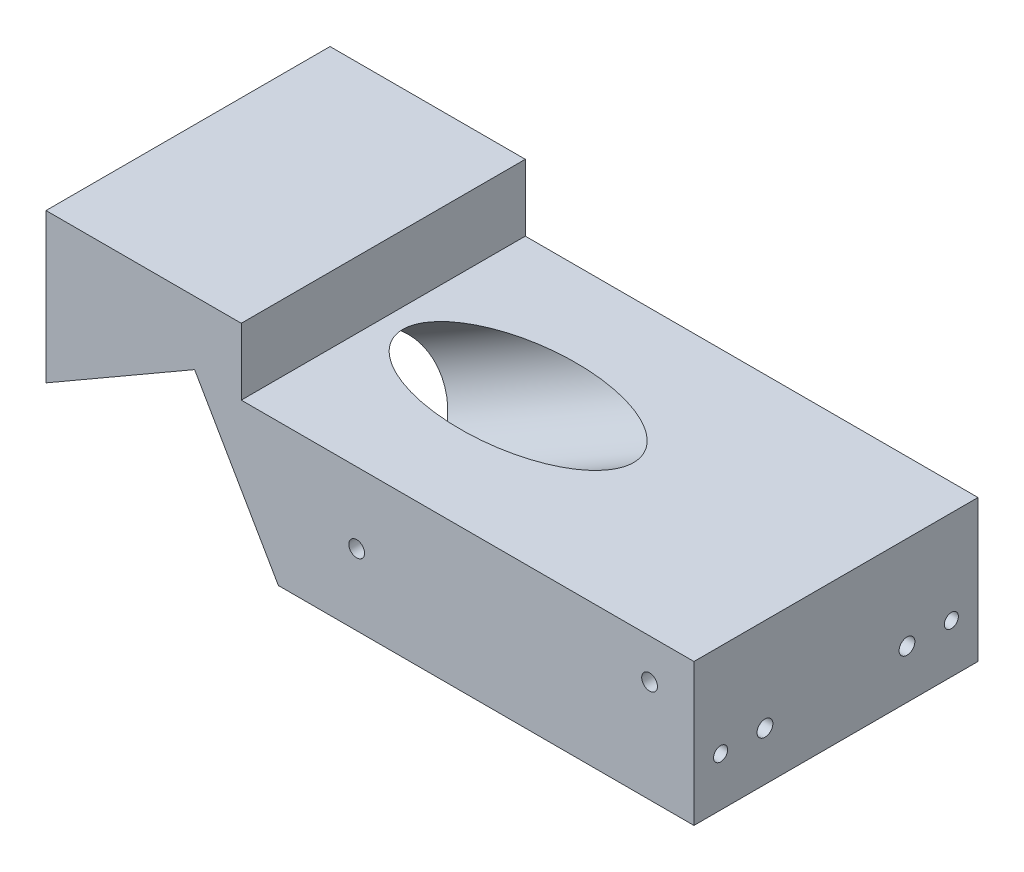
SolidWorks part; units mm, degrees
material "6061-T4 (SS)"
ref_plane "Front Plane" through (0, 0, 0) normal (0, 0, 1) x (1, 0, 0)
ref_plane "Top Plane" through (0, 0, 0) normal (0, 1, 0) x (1, 0, 0)
ref_plane "Right Plane" through (0, 0, 0) normal (1, 0, 0) x (0, 0, -1)
sketch "Sketch1" plane through (0, 0, 0) normal (0, 1, 0) x (1, 0, 0)
  line L1 (-36.5, 16) -> (36.5, 16)
  line L2 (-36.5, 16) -> (-36.5, -16)
  line L3 (-36.5, -16) -> (36.5, -16)
  line L4 (36.5, 16) -> (36.5, -16)
  line L5 (-36.5, 16) -> (36.5, -16) construction
  line L6 (-36.5, -16) -> (36.5, 16) construction
  point P0 (0, 0)
  dimension "D1" = 73
  dimension "D2" = 32
extrude "Boss-Extrude1" add sketch "Sketch1" along normal blind 16
sketch "Sketch78" plane through (0, 0, 16) normal (0, 0, 1) x (1, 0, 0)
  line L1 (-36.5, 16) -> (-14.5, 16)
  line L2 (-36.5, 16) -> (-36.5, 23.5)
  line L3 (-36.5, 23.5) -> (-14.5, 23.5)
  line L4 (-14.5, 16) -> (-14.5, 23.5)
  dimension "D1" = 7.5
  dimension "D2" = 22
extrude "Boss-Extrude4" add sketch "Sketch78" against normal up to surface (32 mm away) up to face at (0, 8, -16)
sketch "Sketch79" plane through (0, 0, -16) normal (0, 0, -1) x (-1, 0, 0)
  line L0 (-32.5, 1.97) -> (23.61, 1.97) construction
  line L1 (-32.5, 1.97) -> (-32.5, 29.2) construction
  line L2 (23.61, 1.97) -> (-20.8992, 27.6674) construction
  line L3 (33.135, 1.97) -> (34.135, 1.97) construction
  line L4 (14.4951, 7.2325) -> (19.7576, 16.3474)
  line L5 (19.7576, 16.3474) -> (36.5, 6.6812)
  line L6 (36.5, 23.5) -> (36.5, 0) construction
  line L7 (14.4951, 7.2325) -> (10.3194, 0)
  line L8 (-36.5, 0) -> (36.5, 0) construction
  line L9 (10.3194, 0) -> (36.5, 0)
  line L10 (36.5, 0) -> (36.5, 6.6812)
  circle A0 centre (23.61, 1.97) radius 9.525 construction
  circle A1 centre (23.61, 1.97) radius 10.525 construction
  dimension "D4" = 19.05
  dimension "D1" = 27.23
  dimension "D2" = 56.11
  dimension "D3" = 30
  dimension "D5" = 1
extrude "Cut-Extrude23" cut sketch "Sketch79" against normal blind 41
sketch "Sketch26" plane through (0, 0, 0) normal (0, -1, 0) x (1, 0, 0)
  line L0 (-10.3194, 16) -> (36.5, 16) construction
  line L1 (36.5, -16) -> (42.85, -16)
  line L2 (36.5, -16) -> (36.5, 16)
  line L3 (36.5, 16) -> (42.85, 16)
  line L4 (42.85, -16) -> (42.85, 16)
  dimension "D1" = 6.35
sketch "Sketch15" plane through (-36.5, 0, 0) normal (-1, 0, 0) x (0, 0, 1)
  line L0 (-10, 14.6812) -> (10, 14.6812) construction
  line L1 (-10, 14.6812) -> (-16, 14.6812) construction
  line L3 (10, 14.6812) -> (16, 14.6812) construction
  line L6 (16, 23.5) -> (16, 6.6812) construction
  line L7 (-16, 23.5) -> (-16, 6.6812) construction
  line L9 (16, 6.6812) -> (-16, 6.6812) construction
  dimension "D3" = 20
  dimension "D4" = 8
sketch "Sketch14" plane through (-13.4261, 5.3809, -20) normal (-0.866, -0.5, 0) x (0, 0, 1)
  line L0 (4, 2.138) -> (20, 2.138) construction
  line L1 (20, 2.138) -> (36, 2.138) construction
  line L2 (36, 12.663) -> (36, -6.2133) construction
  line L3 (4, 12.663) -> (4, -6.2133) construction
  circle A0 centre (20, 2.138) radius 6.5
  dimension "D1" = 13
extrude "Cut-Extrude2" cut sketch "Sketch14" against normal blind 33 and the other way blind 41
hole_wizard "#2-56 Tapped Hole1" positions "Sketch80" profile "Sketch81" tap size "#2-56" standard "ANSI Inch"
sketch "Sketch80" plane through (-36.5, 0, 0) normal (-1, 0, 0) x (0, 0, 1)
  point P0 (-10, 14.6812)
  point P3 (10, 14.6812)
sketch "Sketch81" plane through (-36.5, 14.6812, -10) normal (0, 1, 0) x (0, 0, 1)
  line L0 (0, 0) -> (0, 6.8842)
  line L1 (0, 6.8842) -> (0.889, 6.35)
  line L2 (0.889, 6.35) -> (0.889, 0)
  line L5 (0.889, 0) -> (0, 0)
  line L10 (0, 6.8842) -> (-0.889, 6.35) construction
  line L11 (0, -6.35) -> (0, 107.95) construction
  dimension "Tap Drill Dia." = 1.778
  dimension "Tap Drill Depth" = 6.35
  dimension "Drill Angle" = 118
cosmetic thread "Hole Thread1" parameters "D1"=4.4, "D2"=2.1844
cosmetic thread "Hole Thread2" parameters "D1"=4.4, "D2"=2.1844
sketch "Sketch59" plane through (0, 0, -16) normal (0, 0, -1) x (-1, 0, 0)
  line L0 (36.5, 16) -> (36.5, 0) construction
  line L1 (36.5, 0) -> (-36.5, 0) construction
  line L2 (-36.5, 0) -> (-36.5, 16) construction
  line L3 (36.5, 23.5) -> (36.5, 6.6812) construction
  line L4 (-36.5, 16) -> (36.5, 16) construction
  line L5 (-36.5, 8) -> (36.5, 8) construction
  line L7 (-36.5, 16) -> (14.5, 16) construction
  line L8 (-31.5, 11.5) -> (-31.5, 8) construction
  line L10 (-36.5, 16) -> (-36.5, 0) construction
  point P10 (-31.5, 11.5)
  point P11 (1.5, 8)
  dimension "D1" = 5
  dimension "D2" = 35
  dimension "D3" = 3.5
hole_wizard "#2-56 Tapped Hole2" positions "Sketch82" profile "Sketch83" tap size "#2-56" standard "ANSI Inch"
sketch "Sketch82" plane through (0, 0, -16) normal (0, 0, -1) x (-1, 0, 0)
  point P0 (-31.5, 11.5)
  point P3 (1.5, 8)
sketch "Sketch83" plane through (31.5, 11.5, -16) normal (1, 0, 0) x (0, 1, 0)
  line L0 (0, 0) -> (0, 6.8842)
  line L1 (0, 6.8842) -> (0.889, 6.35)
  line L2 (0.889, 6.35) -> (0.889, 0)
  line L5 (0.889, 0) -> (0, 0)
  line L10 (0, 6.8842) -> (-0.889, 6.35) construction
  line L11 (0, -6.35) -> (0, 107.95) construction
  dimension "Tap Drill Dia." = 1.778
  dimension "Tap Drill Depth" = 6.35
  dimension "Drill Angle" = 118
cosmetic thread "Hole Thread3" parameters "D1"=4.4, "D2"=2.1844
cosmetic thread "Hole Thread4" parameters "D1"=4.4, "D2"=2.1844
hole_wizard "#2-56 Tapped Hole3" positions "Sketch84" profile "Sketch85" tap size "#2-56" standard "ANSI Inch"
sketch "Sketch84" plane through (0, 0, 16) normal (0, 0, 1) x (1, 0, 0)
  point P0 (-1.5, 8)
  point P3 (31.5, 11.5)
sketch "Sketch85" plane through (-1.5, 8, 16) normal (1, 0, 0) x (0, -1, 0)
  line L0 (0, 0) -> (0, 6.8842)
  line L1 (0, 6.8842) -> (0.889, 6.35)
  line L2 (0.889, 6.35) -> (0.889, 0)
  line L5 (0.889, 0) -> (0, 0)
  line L10 (0, 6.8842) -> (-0.889, 6.35) construction
  line L11 (0, -6.35) -> (0, 107.95) construction
  dimension "Tap Drill Dia." = 1.778
  dimension "Tap Drill Depth" = 6.35
  dimension "Drill Angle" = 118
cosmetic thread "Hole Thread5" parameters "D1"=4.4, "D2"=2.1844
cosmetic thread "Hole Thread6" parameters "D1"=4.4, "D2"=2.1844
hole_wizard "#2-56 Tapped Hole4" positions "Sketch86" profile "Sketch87" tap size "#2-56" standard "ANSI Inch"
sketch "Sketch86" plane through (-7.7395, -4.4684, 0) normal (-0.866, -0.5, 0) x (0, 0, 1)
  line L0 (-10, 13.5111) -> (10, 13.5111) construction
  circle A1 centre (0, 13.5111) radius 6.5
  circle A2 centre (0, 13.5111) radius 6.5 construction
  point P0 (-10, 13.5111)
  point P2 (10, 13.5111)
  point P19 (0, 13.5111)
  dimension "D1" = 10
sketch "Sketch87" plane through (-14.4951, 7.2325, -10) normal (0, 0, 1) x (0.5, -0.866, 0)
  line L0 (0, 0) -> (0, 6.8842)
  line L1 (0, 6.8842) -> (0.889, 6.35)
  line L2 (0.889, 6.35) -> (0.889, 0)
  line L5 (0.889, 0) -> (0, 0)
  line L10 (0, 6.8842) -> (-0.889, 6.35) construction
  line L11 (0, -6.35) -> (0, 107.95) construction
  dimension "Tap Drill Dia." = 1.778
  dimension "Tap Drill Depth" = 6.35
  dimension "Drill Angle" = 118
cosmetic thread "Hole Thread7" parameters "D1"=4.4, "D2"=2.1844
cosmetic thread "Hole Thread8" parameters "D1"=4.4, "D2"=2.1844
hole_wizard "#2-56 Tapped Hole5" positions "Sketch89" profile "Sketch90" tap size "#2-56" standard "ANSI Inch"
sketch "Sketch89" plane through (0, 0, -16) normal (0, 0, -1) x (-1, 0, 0)
  line L0 (36.5, 19) -> (31.5, 19) construction
  line L1 (36.5, 23.5) -> (36.5, 6.6812) construction
  line L2 (31.5, 19) -> (31.5, 23.5) construction
  line L3 (36.5, 23.5) -> (14.5, 23.5) construction
  point P0 (31.5, 19)
  dimension "D1" = 4.5
  dimension "D2" = 5
sketch "Sketch90" plane through (-31.5, 19, -16) normal (1, 0, 0) x (0, 1, 0)
  line L0 (0, 0) -> (0, 5.2942)
  line L1 (0, 5.2942) -> (0.889, 4.76)
  line L2 (0.889, 4.76) -> (0.889, 0)
  line L5 (0.889, 0) -> (0, 0)
  line L10 (0, 5.2942) -> (-0.889, 4.76) construction
  line L11 (0, -6.35) -> (0, 107.95) construction
  dimension "Tap Drill Dia." = 1.778
  dimension "Tap Drill Depth" = 4.76
  dimension "Drill Angle" = 118
cosmetic thread "Hole Thread9" parameters "D1"=4.37, "D2"=2.1844
hole_wizard "#2-56 Tapped Hole7" positions "Sketch103" profile "Sketch104" tap size "#2-56" standard "ANSI Inch"
sketch "Sketch103" plane through (36.5, 0, 0) normal (1, 0, 0) x (0, 0, -1)
  line L0 (-16, 5.5) -> (-8, 5.5) construction
  line L1 (-16, 16) -> (-16, 0) construction
  line L2 (-8, 5.5) -> (8, 5.5) construction
  line L3 (8, 5.5) -> (16, 5.5) construction
  line L4 (16, 16) -> (16, 0) construction
  line L5 (16, 5.5) -> (16, 8) construction
  point P0 (-8, 5.5)
  point P3 (8, 5.5)
  dimension "D1" = 2.5
  dimension "D2" = 8
sketch "Sketch104" plane through (36.5, 5.5, 8) normal (0, 1, 0) x (0, 0, -1)
  line L0 (0, 0) -> (0, 13.5342)
  line L1 (0, 13.5342) -> (0.889, 13)
  line L2 (0.889, 13) -> (0.889, 0)
  line L5 (0.889, 0) -> (0, 0)
  line L10 (0, 13.5342) -> (-0.889, 13) construction
  line L11 (0, -6.35) -> (0, 107.95) construction
  dimension "Tap Drill Dia." = 1.778
  dimension "Tap Drill Depth" = 13
  dimension "Drill Angle" = 118
cosmetic thread "Hole Thread10" parameters "D1"=4.37, "D2"=2.1844
cosmetic thread "Hole Thread11" parameters "D1"=4.37, "D2"=2.1844
hole_wizard "1/16 (0.0625) Dowel Hole1" positions "Sketch105" profile "Sketch106" hole size "1/16" standard "ANSI Inch"
sketch "Sketch105" plane through (36.5, 0, 0) normal (1, 0, 0) x (0, 0, -1)
  line L0 (-13, 5.5) -> (-8, 5.5) construction
  line L1 (-8, 5.5) -> (8, 5.5) construction
  line L2 (8, 5.5) -> (13, 5.5) construction
  line L7 (-16, 16) -> (-16, 0) construction
  point P0 (13, 5.5)
  point P2 (-13, 5.5)
  dimension "D1" = 3
sketch "Sketch106" plane through (36.5, 5.5, -13) normal (0, 1, 0) x (0, 0, -1)
  line L0 (0, 0) -> (0, 6.9769)
  line L1 (0, 6.9769) -> (0.7937, 6.5)
  line L2 (0.7937, 6.5) -> (0.7937, 0)
  line L5 (0.7937, 0) -> (0, 0)
  line L10 (0, 6.9769) -> (-0.7938, 6.5) construction
  line L11 (0, -6.35) -> (0, 107.95) construction
  dimension "Hole Dia." = 1.5875
  dimension "Hole Depth" = 6.5
  dimension "Drill Angle" = 118
